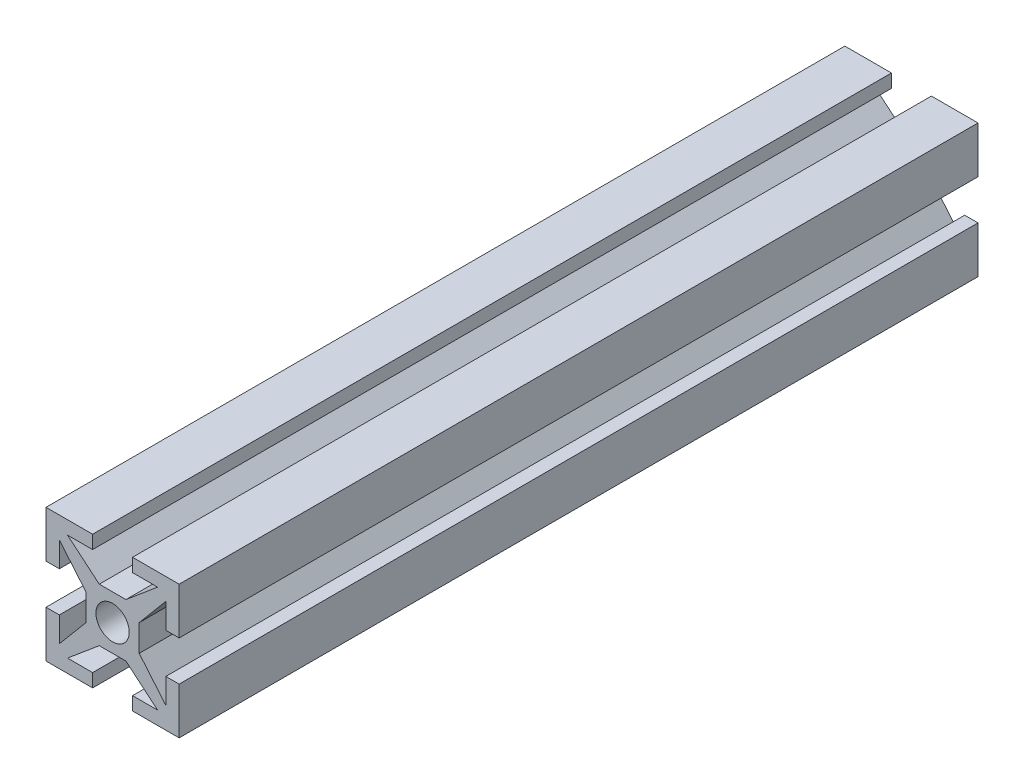
SolidWorks part; units mm, degrees
ref_plane "Front Plane" through (0, 0, 0) normal (0, 0, 1) x (1, 0, 0)
ref_plane "Top Plane" through (0, 0, 0) normal (0, 1, 0) x (1, 0, 0)
ref_plane "Right Plane" through (0, 0, 0) normal (1, 0, 0) x (0, 0, -1)
sketch "Esquisse2" plane through (0, 0, 0) normal (0, 0, 1) x (1, 0, 0)
  line L0 (-1, -2) -> (1, -2)
  line L1 (1, -2) -> (3.3835, -4)
  line L2 (3.3835, -4) -> (1.5, -4)
  line L3 (1.5, -4) -> (1.5, -5)
  line L4 (1.5, -5) -> (5, -5)
  line L5 (-1, -2) -> (-3.3835, -4)
  line L6 (-3.3835, -4) -> (-1.5, -4)
  line L7 (-1.5, -4) -> (-1.5, -5)
  line L8 (-1.5, -5) -> (-5, -5)
  line L9 (-5, -5) -> (-5, -1.5)
  line L10 (-5, -1.5) -> (-4, -1.5)
  line L11 (-4, -1.5) -> (-4, -3.3835)
  line L12 (-4, -3.3835) -> (-2, -1)
  line L13 (-2, -1) -> (-2, 1)
  line L14 (-2, 1) -> (-4, 3.3835)
  line L15 (-4, 3.3835) -> (-4, 1.5)
  line L16 (-4, 1.5) -> (-5, 1.5)
  line L17 (-5, 1.5) -> (-5, 5)
  line L18 (-5, 5) -> (-1.5, 5)
  line L19 (-1.5, 5) -> (-1.5, 4)
  line L20 (-1.5, 4) -> (-3.3835, 4)
  line L21 (-3.3835, 4) -> (-1, 2)
  line L22 (-1, 2) -> (1, 2)
  line L23 (1, 2) -> (3.3835, 4)
  line L24 (3.3835, 4) -> (1.5, 4)
  line L25 (1.5, 4) -> (1.5, 5)
  line L26 (1.5, 5) -> (5, 5)
  line L27 (5, 5) -> (5, 1.5)
  line L28 (5, 1.5) -> (4, 1.5)
  line L29 (4, 1.5) -> (4, 3.3835)
  line L30 (4, 3.3835) -> (2, 1)
  line L31 (2, -1) -> (2, 1)
  line L32 (2, -1) -> (4, -3.3835)
  line L33 (4, -3.3835) -> (4, -1.5)
  line L34 (4, -1.5) -> (5, -1.5)
  line L35 (5, -1.5) -> (5, -5)
  circle A0 centre (0, 0) radius 1.25
  point P4 (0, -2)
  point P34 (0, 2)
  point P40 (2, 0)
  dimension "D4" = 2.5
  dimension "D1" = 2
  dimension "D2" = 3.5
  dimension "D3" = 1
  dimension "D5" = 10
  dimension "D6" = 10
  dimension "D7" = 140
  dimension "D8" = 4
  dimension "D9" = 4
  dimension "D10" = 3.5
  dimension "D11" = 3
extrude "Main Extrusion" add sketch "Esquisse2" along normal blind 60
